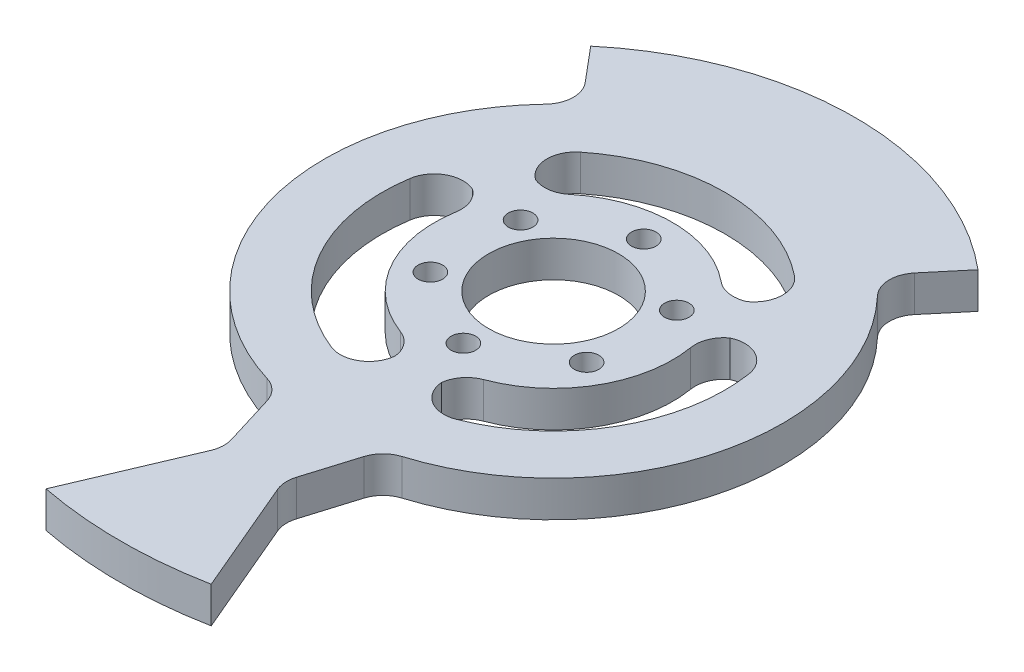
SolidWorks part; units mm, degrees
material "AISI Type A2 Tool Steel"
ref_plane "Front Plane" through (0, 0, 0) normal (0, 0, 1) x (1, 0, 0)
ref_plane "Top Plane" through (0, 0, 0) normal (0, 1, 0) x (1, 0, 0)
ref_plane "Right Plane" through (0, 0, 0) normal (1, 0, 0) x (0, 0, -1)
other "Center of Mass"
other "Bounding Box"
ref_plane "Default Plane" through (0, 2.286, 19.05) normal (0, -1, 0) x (-1, 0, 0)
sketch "Sketch1" plane through (0, 0, 0) normal (0, 1, 0) x (1, 0, 0)
  line L0 (0, -76.2) -> (0, -40.3225) construction
  line L1 (0, -40.3225) -> (0, -11.43) construction
  line L2 (0, -11.43) -> (0, 0) construction
  circle A0 centre (0, 0) radius 76.2 construction
  circle A1 centre (0, 0) radius 11.43
  arc A2 (0, -40.3225) -> (0, 40.3225) centre (0, 0) ccw
  arc A3 (0, 40.3225) -> (0, -76.2) centre (0, -17.9387) ccw construction
  arc A4 (0, 40.3225) -> (0, -40.3225) centre (0, 0) ccw
  dimension "D1" = 152.4
  dimension "D2" = 22.86
  dimension "D3" = 80.645
extrude "Boss-Extrude2" add sketch "Sketch1" along normal mid plane 6.35
sketch "Sketch9" plane through (0, 3.175, 0) normal (0, 1, 0) x (1, 0, 0)
  line L2 (-14.5396, -74.8) -> (-5.1877, -52.7681)
  line L3 (14.5396, -74.8) -> (5.1877, -52.7681)
  line L4 (0, -76.2) -> (0, 0) construction
  line L5 (-5.1877, -52.7681) -> (-9.327, -39.229)
  line L6 (5.1877, -52.7681) -> (9.327, -39.229)
  line L7 (-34.0822, 40.6176) -> (-25.9188, 30.8888)
  line L8 (34.0822, 40.6176) -> (25.9188, 30.8888)
  line L9 (0, 53.0225) -> (0, 0) construction
  line L10 (-5.1877, -52.7681) -> (0, -40.5467) construction
  line L11 (0, -40.5467) -> (5.1877, -52.7681) construction
  line L12 (-14.5396, -74.8) -> (0, 0) construction
  arc A5 (-14.5396, -74.8) -> (14.5396, -74.8) centre (0, 0) ccw
  arc A6 (-5.1877, -52.7681) -> (5.1877, -52.7681) centre (0, 0) ccw construction
  circle A7 centre (0, 0) radius 40.3225 construction
  arc A8 (-9.327, -39.229) -> (9.327, -39.229) centre (0, 0) ccw
  arc A9 (-34.0822, 40.6176) -> (34.0822, 40.6176) centre (0, 0) cw
  arc A10 (25.9188, 30.8888) -> (-25.9188, 30.8888) centre (0, 0) ccw
  dimension "D1" = 76.2
  dimension "D3" = 12.7
  dimension "D5" = 11
  dimension "D2" = 12
  dimension "D4" = 80
  dimension "D6" = 17
extrude "Boss-Extrude4" add sketch "Sketch9" against normal through all
sketch "Sketch6" plane through (0, 3.175, 0) normal (0, 1, 0) x (1, 0, 0)
  line L0 (-23.9377, 18.3511) -> (-15.7556, 13.8157)
  line L1 (15.7556, 13.8157) -> (23.9377, 18.3511)
  line L2 (0, 0) -> (-26.0927, 14.4634) construction
  line L3 (0, 0) -> (26.0927, 14.4634) construction
  line L4 (-23.9377, 18.3511) -> (-26.0927, 14.4634) construction
  line L5 (23.9377, 18.3511) -> (26.0927, 14.4634) construction
  line L6 (0, 0) -> (0, 40.3225) construction
  arc A0 (-15.7556, 13.8157) -> (15.7556, 13.8157) centre (0, 0) cw
  arc A1 (-23.9377, 18.3511) -> (23.9377, 18.3511) centre (0, 0) cw
  circle A2 centre (0, 0) radius 11.43 construction
  arc A4 (29.0716, 27.9418) -> (-0.0952, -40.3224) centre (0, 0) ccw construction
  arc A5 (9.327, -39.229) -> (25.9188, 30.8888) centre (0, 0) ccw construction
  dimension "D3" = 61
  dimension "D4" = 10.16
  dimension "D1" = 9.525
  dimension "D2" = 4.445
  dimension "D5" = 61
extrude "Cut-Extrude2" cut sketch "Sketch6" against normal through all
pattern_circular "CirPattern1" count 3 over 360 about axis through (0, 3.175, 0) along (0, -1, 0) of "Cut-Extrude2"
sketch "Sketch7" [suppressed] plane through (0, 6.35, 0) normal (0, 1, 0) x (1, 0, 0)
  line L0 (12.4559, 70.0208) -> (11.1213, 62.5185)
  line L1 (70.0208, -12.4559) -> (62.5185, -11.1213)
  line L2 (0, 0) -> (52.0712, 36.3433) construction
  line L3 (0, 0) -> (0, 63.5) construction
  line L4 (-6.2364, -4.3527) -> (0, 0) construction
  arc A0 (70.0208, -12.4559) -> (12.4559, 70.0208) centre (0, 0) ccw
  arc A1 (2.4423, -63.453) -> (0, 63.5) centre (0, 0) ccw construction
  arc A2 (62.5185, -11.1213) -> (11.1213, 62.5185) centre (0, 0) ccw
  dimension "D1" = 7.62
  dimension "D3" = 90
sketch "Sketch10" plane through (0, 3.175, 0) normal (0, 1, 0) x (1, 0, 0)
  line L0 (0, 20.955) -> (0, 15.875) construction
  line L1 (0, 15.875) -> (0, 11.43) construction
  circle A0 centre (0, 15.875) radius 2.159
  circle A1 centre (0, 15.875) radius 3.9624 construction
  circle A2 centre (0, 0) radius 11.43 construction
  arc A3 (4.0869, -20.5526) -> (19.8425, 6.7369) centre (0, 0) ccw construction
  dimension "D1" = 4.318
  dimension "D2" = 7.9248
  dimension "D3" = 15.875
extrude "Cut-Extrude3" cut sketch "Sketch10" against normal through all
pattern_circular "CirPattern8" count 6 over 360 about axis through (0, 3.175, 0) along (0, -1, 0) of "Cut-Extrude3" reverse direction yes
fillet "Fillet3" radius 5.08 12 edges at (-23.9377, 0, -18.3511) (23.9377, 0, -18.3511) (15.7556, 0, -13.8157) (-15.7556, 0, -13.8157) (3.9237, 0, 29.9062) (27.8614, 0, -11.5551) (19.8425, 0, -6.7369) (4.0869, 0, 20.5526) (-3.9237, 0, 29.9062) (-4.0869, 0, 20.5526) (-19.8425, 0, -6.7369) (-27.8614, 0, -11.5551)
other "Center of Mass Reference Point2"
fillet "Fillet4" radius 5.08 6 edges at (-5.1877, 0, 52.7681) (-9.327, 0, 39.229) (5.1877, 0, 52.7681) (9.327, 0, 39.229) (25.9188, 0, -30.8888) (-25.9188, 0, -30.8888)
equation "\"Unit Measure\"= \"BoundingVolume\" / \"Thickness\"'in^2"
